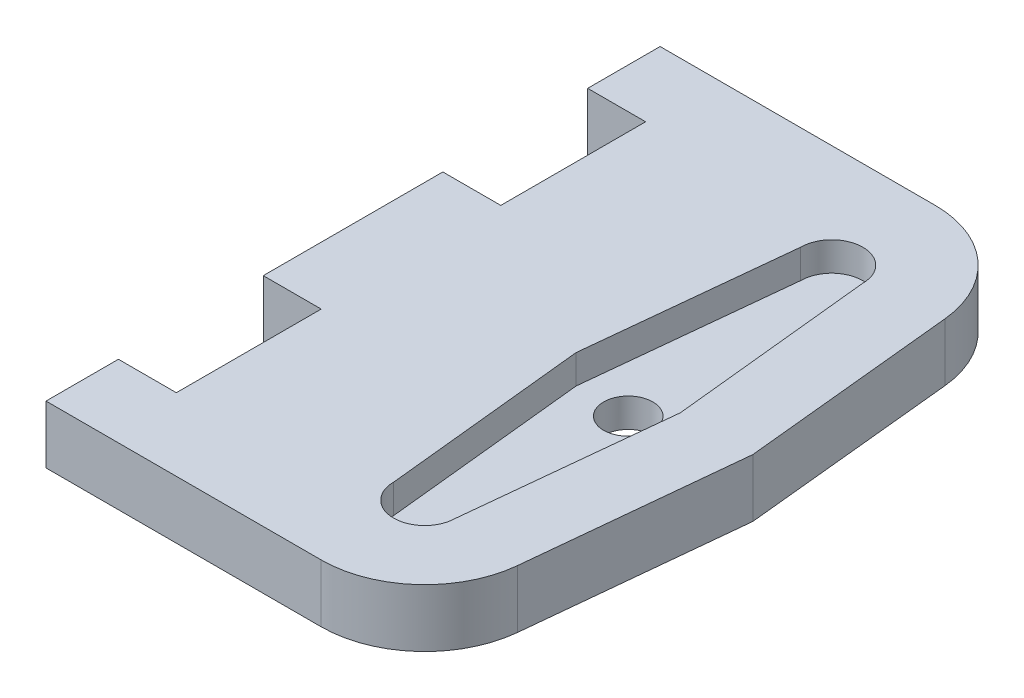
SolidWorks part; units mm, degrees
ref_plane "Front Plane" through (0, 0, 0) normal (0, 0, 1) x (1, 0, 0)
ref_plane "Top Plane" through (0, 0, 0) normal (0, 1, 0) x (1, 0, 0)
ref_plane "Right Plane" through (0, 0, 0) normal (1, 0, 0) x (0, 0, -1)
sketch "Sketch1" plane through (0, 0, 0) normal (0, 1, 0) x (1, 0, 0)
  line L1 (0, 0) -> (20, 0)
  line L2 (0, 0) -> (0, 50)
  line L3 (0, 50) -> (20, 50)
  line L4 (20, 0) -> (20, 50)
  dimension "D1" = 50
  dimension "D2" = 20
extrude "Boss-Extrude2" add sketch "Sketch1" along normal blind 4
sketch "Sketch3" plane through (0, 4, 0) normal (0, 1, 0) x (1, 0, 0)
  line L0 (7.85, 10.95) -> (6.4, 25)
  line L1 (6.4, 25) -> (7.85, 39.05)
  line L2 (12.15, 39.05) -> (13.6, 25)
  line L3 (13.6, 25) -> (12.15, 10.95)
  line L4 (6.4, 25) -> (13.6, 25) construction
  line L5 (20, 50) -> (0, 50) construction
  line L6 (0, 50) -> (0, 0) construction
  arc A0 (12.15, 39.05) -> (7.85, 39.05) centre (10, 39.05) ccw
  arc A1 (7.85, 10.95) -> (12.15, 10.95) centre (10, 10.95) ccw
  point P12 (10, 50)
  point P15 (0, 25)
  dimension "D1" = 4.3
  dimension "D2" = 4.3
  dimension "D3" = 28.1
  dimension "D4" = 14.05
  dimension "D5" = 7.2
  dimension "D6" = 3.6
  dimension "D7" = 3.6
extrude "Cut-Extrude1" cut sketch "Sketch3" against normal blind 2
sketch "Sketch7" plane through (0, 4, 0) normal (0, 1, 0) x (1, 0, 0)
  line L0 (17.1141, 39.7659) -> (18.6, 25)
  line L1 (18.6, 25) -> (17.1141, 10.2341)
  line L4 (10, 46.2) -> (0, 46.2)
  line L5 (0, 50) -> (0, 0) construction
  line L6 (10, 3.8) -> (0, 3.8)
  line L7 (0, 3.8) -> (0, 0)
  line L8 (20, 50) -> (0, 50)
  line L9 (20, 50) -> (20, 0)
  line L10 (20, 0) -> (0, 0)
  line L11 (0, 50) -> (0, 46.2)
  arc A0 (17.1141, 39.7659) -> (10, 46.2) centre (10, 39.05) ccw
  arc A1 (10, 3.8) -> (17.1141, 10.2341) centre (10, 10.95) ccw
  arc A3 (12.15, 39.05) -> (7.85, 39.05) centre (10, 39.05) ccw construction
  arc A4 (7.85, 10.95) -> (12.15, 10.95) centre (10, 10.95) ccw construction
  dimension "D1" = 5
  dimension "D2" = 5
  dimension "D3" = 5
extrude "Cut-Extrude2" cut sketch "Sketch7" against normal through all both and the other way through all
sketch "Sketch8" plane through (0, 0, 0) normal (0, -1, 0) x (1, 0, 0)
  line L1 (0, -46.2) -> (-64.2367, -46.2)
  line L2 (0, -46.2) -> (0, -3.8)
  line L3 (0, -3.8) -> (-64.2367, -3.8)
  line L4 (-64.2367, -46.2) -> (-64.2367, -3.8)
extrude "Boss-Extrude4" add sketch "Sketch8" against normal blind 4
sketch "Sketch9" plane through (0, 2, 0) normal (0, 1, 0) x (1, 0, 0)
  circle A0 centre (10, 25) radius 1.7
  dimension "D1" = 3.4
  dimension "D2" = 3.6
extrude "Cut-Extrude4" cut sketch "Sketch9" against normal blind 4
sketch "Sketch10" plane through (0, 0, 0) normal (0, -1, 0) x (1, 0, 0)
  line L0 (-64.2367, -46.2) -> (10, -46.2) construction
  line L1 (-64.2367, -3.8) -> (-11, -3.8)
  line L2 (-64.2367, -3.8) -> (-64.2367, -46.2)
  line L3 (-64.2367, -46.2) -> (-11, -46.2)
  line L4 (-11, -3.8) -> (-11, -46.2)
  circle A0 centre (10, -25) radius 1.7
  dimension "D1" = 21
extrude "Cut-Extrude5" cut sketch "Sketch10" against normal blind 4
sketch "Sketch11" plane through (0, 0, 0) normal (0, -1, 0) x (1, 0, 0)
  line L0 (-11, -46.2) -> (10, -46.2) construction
  line L1 (-11, -3.8) -> (-5, -3.8)
  line L2 (-11, -3.8) -> (-11, -46.2)
  line L3 (-11, -46.2) -> (-5, -46.2)
  line L4 (-5, -3.8) -> (-5, -46.2)
  dimension "D1" = 6
extrude "Boss-Extrude5" add sketch "Sketch11" along normal blind 62.2
sketch "Sketch13" plane through (-5, 0, 0) normal (1, 0, 0) x (0, 0, -1)
  line L0 (46.2, -62.2) -> (46.2, 0) construction
  line L1 (3.8, -62.2) -> (46.2, -62.2)
  line L2 (3.8, -62.2) -> (3.8, -58.2)
  line L3 (3.8, -58.2) -> (46.2, -58.2)
  line L4 (46.2, -62.2) -> (46.2, -58.2)
  dimension "D1" = 4
extrude "Boss-Extrude6" add sketch "Sketch13" along normal blind 30
sketch "Sketch14" plane through (0, -58.2, 0) normal (0, 1, 0) x (1, 0, 0)
  line L0 (-5, 46.2) -> (-5, 3.8) construction
  line L2 (-5, 3.8) -> (15.3097, 16.5261)
  line L3 (-5, 46.2) -> (15.3097, 33.4739)
  circle A0 centre (10, 25) radius 5
  arc A1 (15.3097, 16.5261) -> (15.3097, 33.4739) centre (10, 25) ccw
  line M6 (-5, 3.8) -> (25, 3.8)
  line M7 (25, 3.8) -> (25, 46.2)
  line M8 (25, 46.2) -> (-5, 46.2)
  dimension "D1" = 10
  dimension "D4" = 20
  dimension "D2" = 15
  dimension "D3" = 21.2
extrude "Cut-Extrude6" cut sketch "Sketch14" against normal blind 30 contours A1 L2 L3 M6 M7 M8 | A0 region at (5.4307, -58.2, -9.7229) region at (10, -58.2, -25)
sketch "Sketch15" plane through (0, 0, -3.8) normal (0, 0, 1) x (1, 0, 0)
  line L0 (-5, -62.2) -> (-11, -62.2) construction
  line L1 (-11, 4) -> (-9, 4)
  line L2 (-11, 4) -> (-11, -62.2)
  line L3 (-11, -62.2) -> (-9, -62.2)
  line L4 (-9, 4) -> (-9, -62.2)
  dimension "D1" = 4
extrude "Cut-Extrude7" cut sketch "Sketch15" against normal through all both and the other way through all
sketch "Sketch16" plane through (-5, 0, 0) normal (1, 0, 0) x (0, 0, -1)
  line L0 (3.8, 0) -> (10, -19.1)
  line L2 (10, -39.1) -> (3.8, -58.2)
  line L4 (46.2, -58.2) -> (40, -39.1)
  line L6 (40, -19.1) -> (46.2, 0)
  line L8 (40, -19.1) -> (30, -19.1)
  line L9 (30, -19.1) -> (30, -39.1)
  line L10 (30, -39.1) -> (40, -39.1)
  line L11 (10, -39.1) -> (20, -39.1)
  line L12 (20, -39.1) -> (20, -19.1)
  line L13 (20, -19.1) -> (10, -19.1)
  line L14 (46.2, -58.2) -> (46.2, 0) construction
  line L16 (3.8, 0) -> (3.8, -58.2)
  line L17 (46.2, -58.2) -> (46.2, 0)
  dimension "D1" = 10
  dimension "D2" = 10
  dimension "D3" = 10
  dimension "D4" = 6.2
  dimension "D5" = 20
  dimension "D6" = 19.1
extrude "Cut-Extrude8" cut sketch "Sketch16" against normal through all both and the other way through all
sketch "Sketch17" plane through (0, 0, -3.8) normal (0, 0, 1) x (1, 0, 0)
  line L1 (-9, 0) -> (27.2031, 0)
  line L2 (-9, 0) -> (-9, -88.0545)
  line L3 (-9, -88.0545) -> (27.2031, -88.0545)
  line L4 (27.2031, 0) -> (27.2031, -88.0545)
extrude "Cut-Extrude9" cut sketch "Sketch17" against normal through all both and the other way through all
sketch "Sketch18" plane through (-9, 0, 0) normal (-1, 0, 0) x (0, 0, 1)
  line L0 (-46.2, 0) -> (-3.8, 0) construction
  line L1 (-8.8, 0) -> (-18.8, 0)
  line L2 (-8.8, 0) -> (-8.8, 4)
  line L3 (-8.8, 4) -> (-18.8, 4)
  line L4 (-18.8, 0) -> (-18.8, 4)
  line L5 (-46.2, 4) -> (-3.8, 4) construction
  line L6 (-3.8, 4) -> (-3.8, 0) construction
  line L7 (-31.2, 0) -> (-41.2, 0)
  line L8 (-31.2, 0) -> (-31.2, 4)
  line L9 (-31.2, 4) -> (-41.2, 4)
  line L10 (-41.2, 0) -> (-41.2, 4)
  line L11 (-46.2, 0) -> (-46.2, 4) construction
  dimension "D1" = 5
  dimension "D2" = 10
  dimension "D3" = 5
  dimension "D4" = 10
extrude "Cut-Extrude10" cut sketch "Sketch18" against normal blind 4
